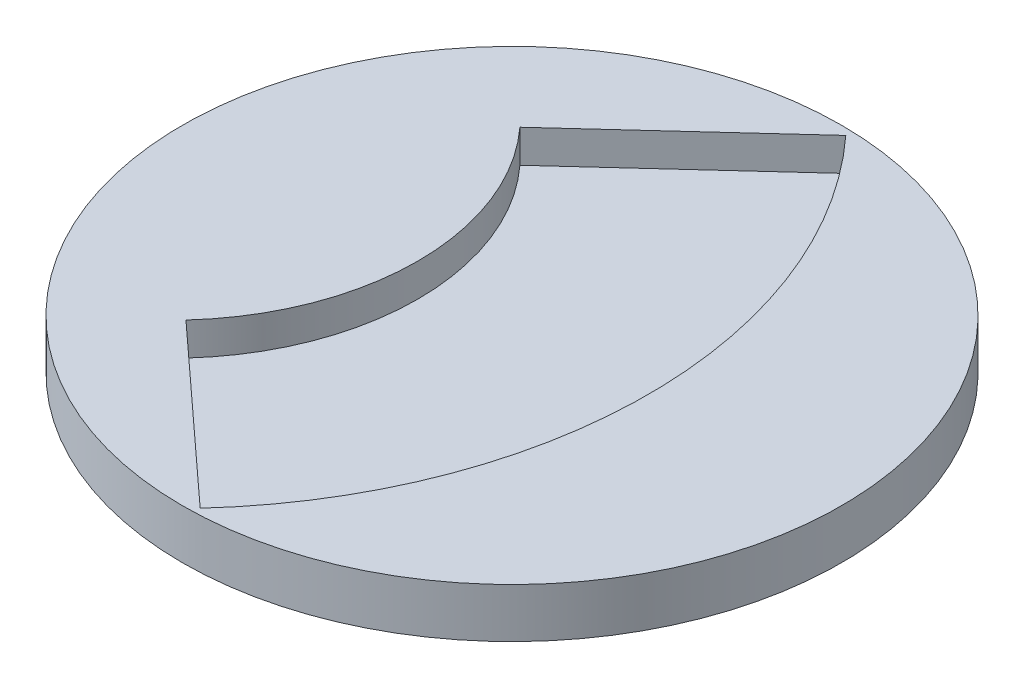
SolidWorks part; units mm, degrees
ref_plane "Front Plane" through (0, 0, 0) normal (0, 0, 1) x (1, 0, 0)
ref_plane "Top Plane" through (0, 0, 0) normal (0, 1, 0) x (1, 0, 0)
ref_plane "Right Plane" through (0, 0, 0) normal (1, 0, 0) x (0, 0, -1)
sketch "Sketch1" plane through (0, 0, 0) normal (0, 0, 1) x (1, 0, 0)
  line L0 (1.05, -2) -> (1.05, 2)
  line L1 (1.05, 2) -> (0, 2)
  line L2 (0, 2) -> (0, 5)
  line L3 (0, 5) -> (20, 5)
  line L4 (20, 5) -> (20, 2)
  line L5 (20, 2) -> (3.05, 2)
  line L6 (3.05, 2) -> (3.05, -2)
  line L7 (3.05, -2) -> (1.05, -2)
  line L8 (0, -3.5392) -> (0, 6.3608) construction
  point P9 (1.05, 0)
  dimension "D1" = 2.1
  dimension "D2" = 2
  dimension "D3" = 3
  dimension "D4" = 4
  dimension "D5" = 40
revolve "Revolve1" add sketch "Sketch1" angle 360 about L8
sketch "Sketch2" plane through (0, 5, 0) normal (0, 1, 0) x (1, 0, 0)
  line L0 (0.6675, 19.5921) -> (-9.6544, 10.1339)
  line L1 (0.6675, -19.5921) -> (-9.6544, -10.1339)
  line L2 (8.2865, 0) -> (-5.7135, 0) construction
  arc A0 (0.6675, 19.5921) -> (0.6675, -19.5921) centre (-20.7135, 0) cw
  arc A1 (-9.6544, 10.1339) -> (-9.6544, -10.1339) centre (-20.7135, 0) cw
  dimension "IR" = 15
  dimension "OR" = 29
  dimension "D1" = 20.7135
extrude "Cut-Extrude1" cut sketch "Sketch2" against normal blind 2
equation "\"D1@Sketch2\"=2*(\"OR@Sketch2\"^3-\"IR@Sketch2\"^3)*sin(\"a@Sketch2\")/(3*\"a@Sketch2\"*(\"OR@Sketch2\"^2-\"IR@Sketch2\"^2))"
